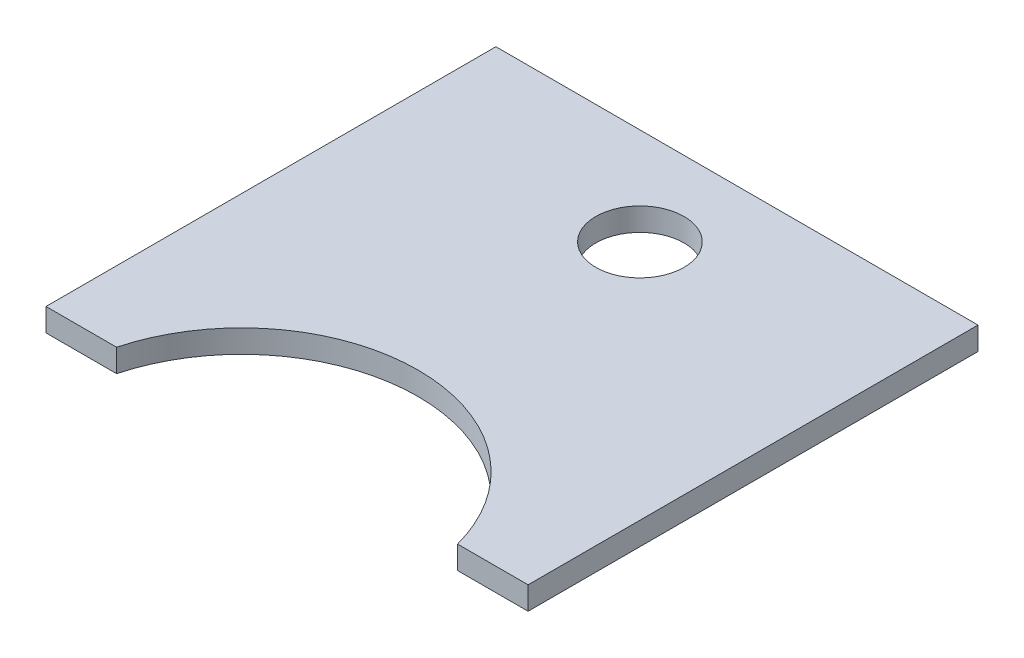
SolidWorks part; units mm, degrees
ref_plane "Front Plane" through (0, 0, 0) normal (0, 0, 1) x (1, 0, 0)
ref_plane "Top Plane" through (0, 0, 0) normal (0, 1, 0) x (1, 0, 0)
ref_plane "Right Plane" through (0, 0, 0) normal (1, 0, 0) x (0, 0, -1)
sketch "Sketch1" plane through (0, 0, 0) normal (0, 1, 0) x (1, 0, 0)
  line L2 (-17.3513, 3.2719) -> (-12.2713, 3.2719)
  line L3 (17.3513, 3.2719) -> (12.2713, 3.2719)
  line L4 (-17.3513, 3.2719) -> (-17.3513, 35.6569)
  line L5 (-17.3513, 35.6569) -> (17.3513, 35.6569)
  line L6 (17.3513, 35.6569) -> (17.3513, 3.2719)
  circle A0 centre (0, 0) radius 12.7 construction
  circle A1 centre (0, 28.6719) radius 3.175
  arc A4 (-12.2713, 3.2719) -> (12.2713, 3.2719) centre (0, 0) cw
  point P6 (0, 0)
  point P8 (0, 0)
  point P13 (0, 0)
  dimension "D1" = 6.35
  dimension "D2" = 25.4
  dimension "D4" = 5.08
  dimension "D5" = 25.4
extrude "Boss-Extrude1" add sketch "Sketch1" along normal blind 1.651
fillet "Fillet1" radius 0.762 rebuild error yes
